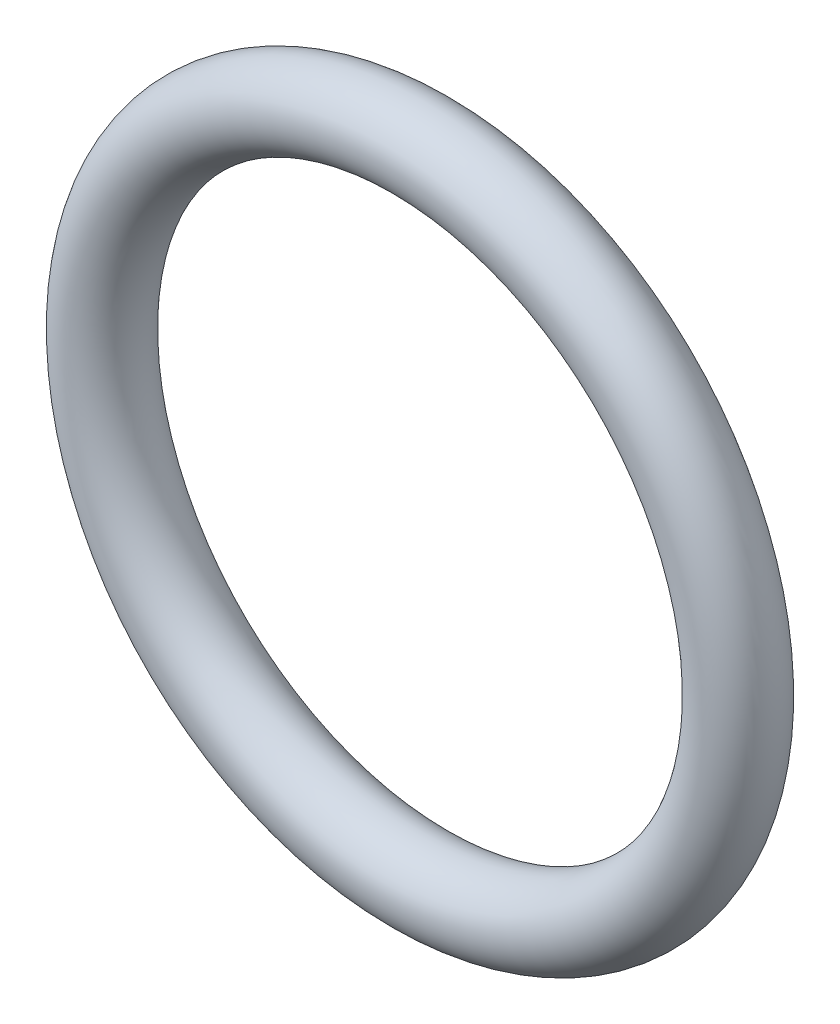
SolidWorks part; units mm, degrees
material "Rubber"
ref_plane "Front Plane" through (0, 0, 0) normal (0, 0, 1) x (1, 0, 0)
ref_plane "Top Plane" through (0, 0, 0) normal (0, 1, 0) x (1, 0, 0)
ref_plane "Right Plane" through (0, 0, 0) normal (1, 0, 0) x (0, 0, -1)
sketch "Sketch1" plane through (0, 0, 0) normal (0, 0, 1) x (1, 0, 0)
  line L0 (0, 12.4968) -> (0, 16.0274) construction
  line L1 (0, 0) -> (13.402, -4.8779) construction
  circle A0 centre (0, 0) radius 14.2621 construction
  circle A1 centre (0, 0) radius 12.4968
  circle A2 centre (0, 0) radius 16.0274
  point P3 (0, 14.2621)
  point P8 (13.402, -4.8779)
  dimension "D1" = 110
  dimension "OD" = 32.0548
  dimension "ID" = 24.9936
  dimension "Width" = 3.5306
sketch "Sketch3" plane through (0, 0, 0) normal (0, 0, 1) x (1, 0, 0)
  circle A0 centre (0, 0) radius 14.2621 construction
  circle A1 centre (0, 0) radius 14.2621
sketch "Sketch2" plane through (0, 0, 0) normal (1, 0, 0) x (0, 0, -1)
  circle A0 centre (0, 14.2621) radius 1.7653
sweep "Sweep2" add profiles "Sketch2" path "Sketch3"
